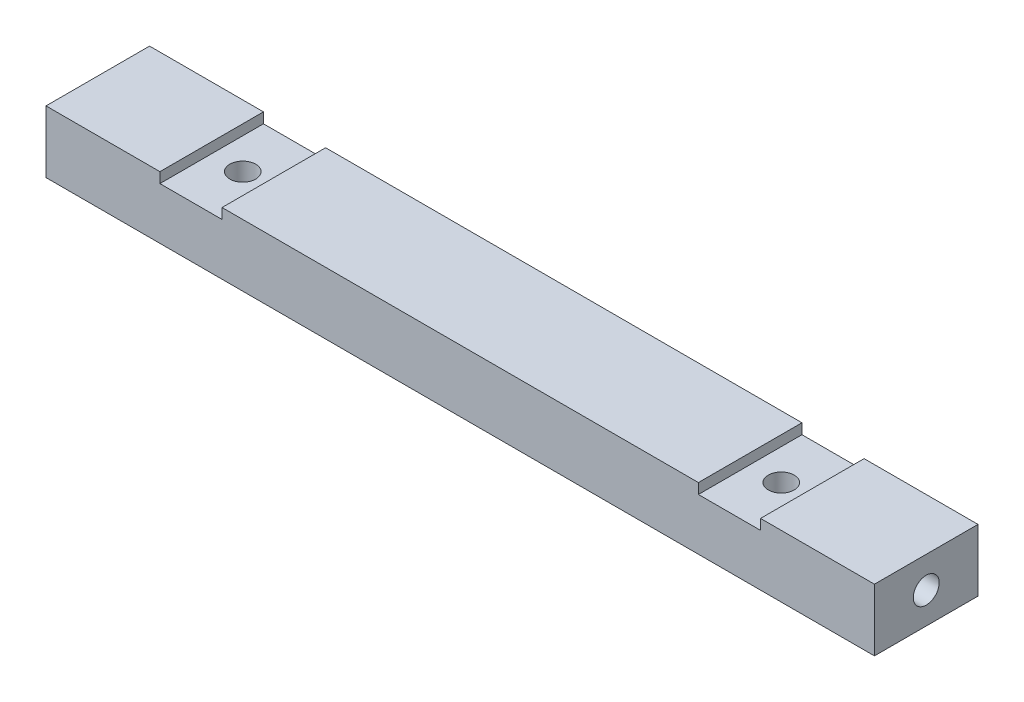
SolidWorks part; units mm, degrees
ref_plane "Front Plane" through (0, 0, 0) normal (0, 0, 1) x (1, 0, 0)
ref_plane "Top Plane" through (0, 0, 0) normal (0, 1, 0) x (1, 0, 0)
ref_plane "Right Plane" through (0, 0, 0) normal (1, 0, 0) x (0, 0, -1)
sketch "Sketch1" plane through (0, 0, 0) normal (0, 1, 0) x (1, 0, 0)
  line L1 (0, 0) -> (80, 0)
  line L2 (0, 0) -> (0, 10)
  line L3 (0, 10) -> (80, 10)
  line L4 (80, 0) -> (80, 10)
  dimension "D1" = 10
  dimension "D2" = 80
extrude "Boss-Extrude1" add sketch "Sketch1" along normal blind 6
sketch "Sketch2" plane through (0, 6, 0) normal (0, 1, 0) x (1, 0, 0)
  line L0 (80, 10) -> (0, 10) construction
  line L1 (11, 10) -> (17, 10)
  line L2 (11, 10) -> (11, 0)
  line L3 (11, 0) -> (17, 0)
  line L4 (17, 10) -> (17, 0)
  line L5 (0, 0) -> (80, 0) construction
  line L7 (69, 10) -> (63, 10)
  line L8 (69, 10) -> (69, 0)
  line L9 (69, 0) -> (63, 0)
  line L10 (63, 10) -> (63, 0)
  line L11 (0, 10) -> (0, 0) construction
  line L12 (80, 0) -> (80, 10) construction
  dimension "D1" = 11
  dimension "D2" = 11
  dimension "D3" = 6
extrude "Cut-Extrude1" cut sketch "Sketch2" against normal blind 1
hole_wizard "Tap Drill for M3x0.5 Tap1" positions "3DSketch1" profile "Sketch5" hole size "M3x0.5" standard "ANSI Metric"
sketch3d "3DSketch1"
  line L0 (0, 0, -10) -> (0, 0, 0) construction
  line L1 (80, 0, -10) -> (0, 0, -10) construction
  line L2 (0, 6, 0) -> (0, 0, 0) construction
  line L3 (80, 0, 0) -> (80, 0, -10) construction
  line L4 (80, 6, 0) -> (80, 0, 0) construction
  point P0 (80, 3, -5)
  point P2 (66, 0, -5)
  point P4 (14, 0, -5)
  point P6 (0, 3, -5)
  dimension "D1" = 14
  dimension "D2" = 5
  dimension "D3" = 3
  dimension "D4" = 5
  dimension "D5" = 14
  dimension "D6" = 5
  dimension "D7" = 5
  dimension "D8" = 3
sketch "Sketch5" plane through (80, 3, -5) normal (0, 1, 0) x (0, 0, -1)
  line L0 (0, 0) -> (0, 10.7511)
  line L1 (0, 10.7511) -> (1.25, 10)
  line L2 (1.25, 10) -> (1.25, 0)
  line L5 (1.25, 0) -> (0, 0)
  line L10 (0, 10.7511) -> (-1.25, 10) construction
  line L11 (0, -6.35) -> (0, 107.95) construction
  dimension "Hole Dia." = 2.5
  dimension "Hole Depth" = 10
  dimension "Drill Angle" = 118
chamfer "Chamfer1" distance 1.5 angle 45 2 edges at (66, 0, -6.25) (14, 0, -6.25)
